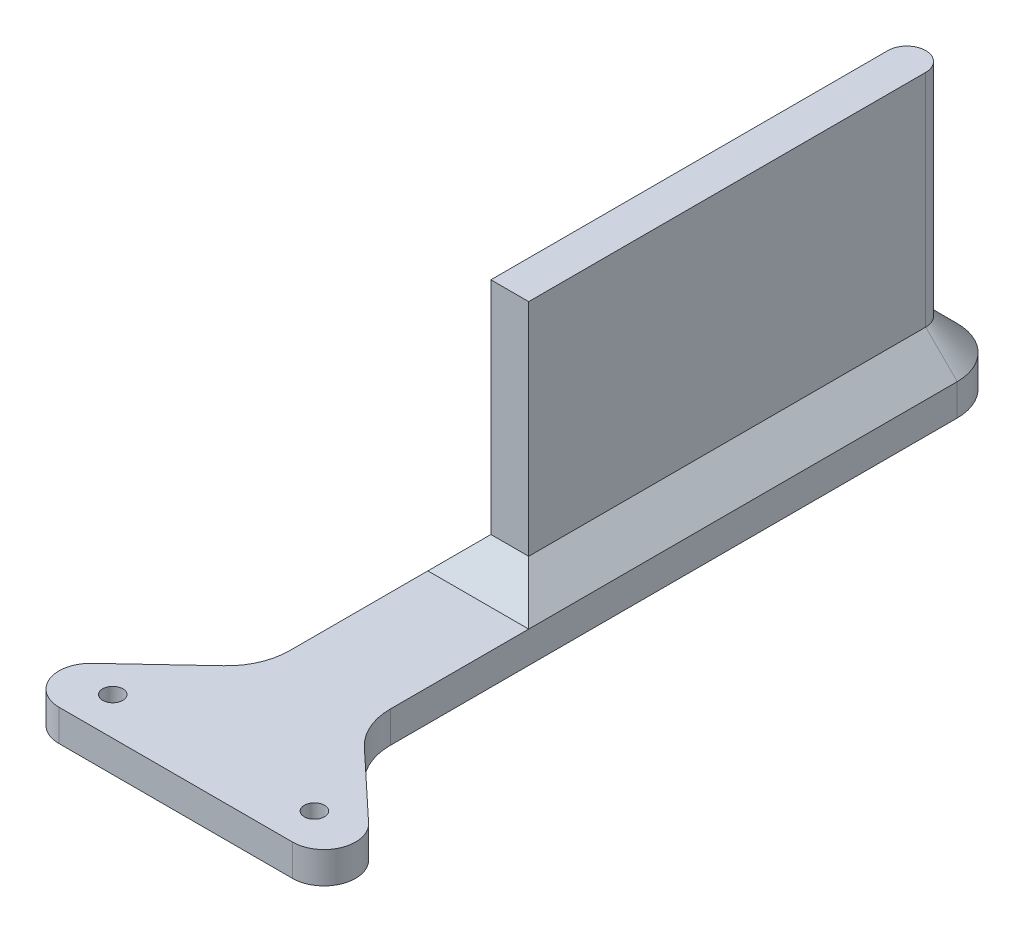
SolidWorks part; units mm, degrees
ref_plane "Front Plane" through (0, 0, 0) normal (0, 0, 1) x (1, 0, 0)
ref_plane "Top Plane" through (0, 0, 0) normal (0, 1, 0) x (1, 0, 0)
ref_plane "Right Plane" through (0, 0, 0) normal (1, 0, 0) x (0, 0, -1)
sketch "Sketch1" plane through (0, 0, 0) normal (0, 1, 0) x (1, 0, 0)
  line L5 (-18.5288, -6) -> (18.5288, -6)
  line L8 (21.9485, 2.6477) -> (11.1606, 12.7613)
  line L9 (-11.1606, 12.7613) -> (-21.9485, 2.6477)
  line L11 (-8, 95) -> (-8, 20.0567)
  line L12 (8, 95) -> (8, 20.0567)
  line L13 (-8, 110) -> (-8, 95)
  line L14 (8, 95) -> (8, 110)
  arc A0 (18.5288, -6) -> (21.9485, 2.6477) centre (18.5288, -1) ccw
  arc A1 (-18.5288, -6) -> (-21.9485, 2.6477) centre (-18.5288, -1) cw
  circle A2 centre (0, 15) radius 1
  circle A3 centre (-16, 0) radius 1
  circle A4 centre (16, 0) radius 1
  arc A6 (11.1606, 12.7613) -> (8, 20.0567) centre (18, 20.0567) cw
  arc A7 (-11.1606, 12.7613) -> (-8, 20.0567) centre (-18, 20.0567) ccw
  arc A8 (8, 110) -> (-8, 110) centre (0, 110) ccw
  point P3 (0, 0)
  dimension "D2" = 5
  dimension "D1" = 10
extrude "Boss-Extrude1" add sketch "Sketch1" along normal blind 3
sketch "Sketch2" plane through (0, 3, 0) normal (0, 1, 0) x (1, 0, 0)
  line L0 (3, 47) -> (-3, 47)
  line L1 (-3, 95) -> (-3, 47)
  line L3 (3, 47) -> (3, 95)
  line L4 (-3, 95) -> (-3, 110)
  line L6 (3, 110) -> (3, 95)
  arc A1 (3, 110) -> (-3, 110) centre (0, 110) ccw
extrude "Boss-Extrude2" add sketch "Sketch2" along normal blind 40
chamfer "Chamfer1" distance 5 angle 45 4 edges at (0, 3, -47) (3, 3, -78.5) (0, 3, -113) (-3, 3, -78.5)
sketch "Sketch3" plane through (0, 3, 0) normal (0, 1, 0) x (1, 0, 0)
  circle A0 centre (-16, 0) radius 1.6
  circle A1 centre (16, 0) radius 1.6
extrude "Cut-Extrude1" cut sketch "Sketch3" against normal blind 10
sketch "Sketch4" plane through (0, 3, 0) normal (0, 1, 0) x (1, 0, 0)
  circle A0 centre (0, 15) radius 1 construction
  circle A1 centre (0, 15) radius 1
extrude "Boss-Extrude3" add sketch "Sketch4" against normal up to surface (3 mm away) up to face at (-16, 0, -1.6)
sketch "Sketch5" plane through (0, 0, 0) normal (0, -1, 0) x (1, 0, 0)
  line L5 (11.1606, -12.7613) -> (21.9485, -2.6477)
  line L6 (18.5288, 6) -> (-18.5288, 6)
  line L7 (-21.9485, -2.6477) -> (-11.1606, -12.7613)
  line L8 (-8, -20.0567) -> (-8, -110)
  line L9 (8, -110) -> (8, -20.0567)
  line L10 (11.1606, -12.7613) -> (21.9485, -2.6477)
  line L11 (18.5288, 6) -> (-18.5288, 6)
  line L12 (-21.9485, -2.6477) -> (-11.1606, -12.7613)
  line L13 (-8, -20.0567) -> (-8, -110)
  line L14 (8, -110) -> (8, -20.0567)
  circle A0 centre (-16, 0) radius 1.6 construction
  circle A1 centre (-16, 0) radius 1.6
  circle A2 centre (16, 0) radius 1.6 construction
  circle A3 centre (16, 0) radius 1.6
  arc A5 (11.1606, -12.7613) -> (8, -20.0567) centre (18, -20.0567) ccw
  arc A6 (21.9485, -2.6477) -> (18.5288, 6) centre (18.5288, 1) ccw
  arc A7 (-18.5288, 6) -> (-21.9485, -2.6477) centre (-18.5288, 1) ccw
  arc A8 (-8, -20.0567) -> (-11.1606, -12.7613) centre (-18, -20.0567) ccw
  arc A9 (-8, -110) -> (8, -110) centre (0, -110) ccw
  arc A10 (11.1606, -12.7613) -> (8, -20.0567) centre (18, -20.0567) ccw
  arc A11 (21.9485, -2.6477) -> (18.5288, 6) centre (18.5288, 1) ccw
  arc A12 (-18.5288, 6) -> (-21.9485, -2.6477) centre (-18.5288, 1) ccw
  arc A13 (-8, -20.0567) -> (-11.1606, -12.7613) centre (-18, -20.0567) ccw
  arc A14 (-8, -110) -> (8, -110) centre (0, -110) ccw
  dimension "D1" = 0
extrude "Boss-Extrude4" add sketch "Sketch5" along normal blind 2
